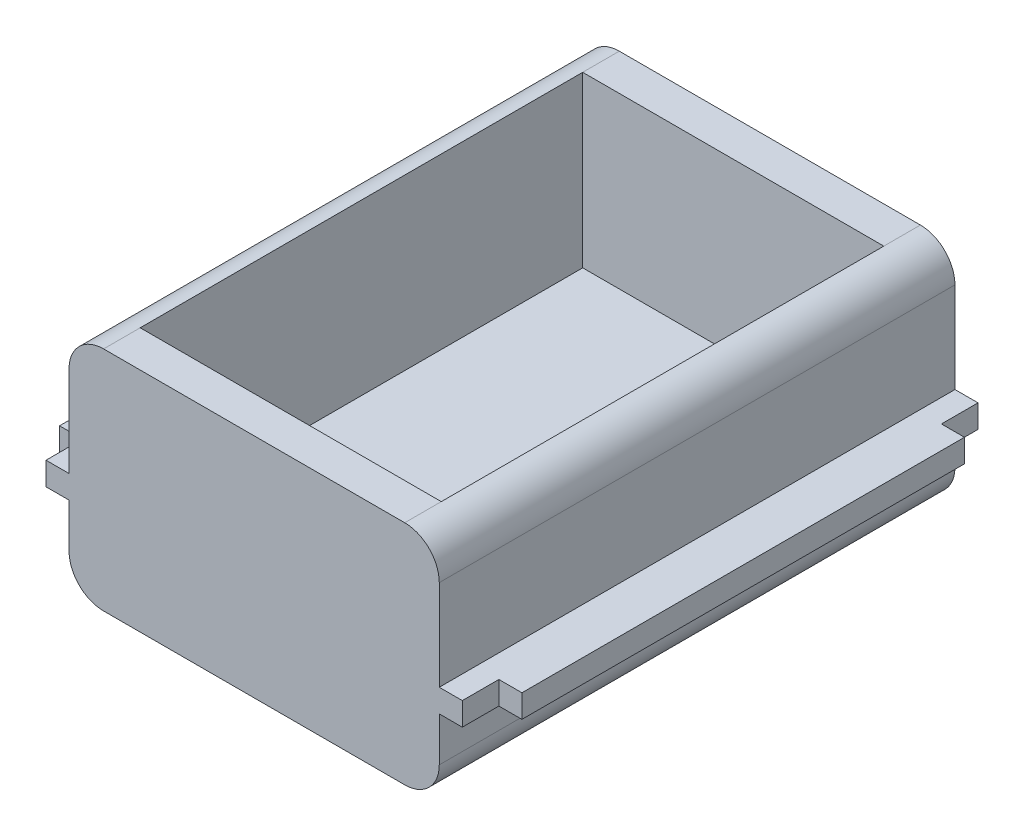
SolidWorks part; units mm, degrees
note: The reader was unsure of these and kept them because the rebuilt part matched: shared geometry of "Sketch5<4>".
ref_plane "Front Plane" through (0, 0, 0) normal (0, 0, 1) x (1, 0, 0)
ref_plane "Top Plane" through (0, 0, 0) normal (0, 1, 0) x (1, 0, 0)
ref_plane "Right Plane" through (0, 0, 0) normal (1, 0, 0) x (0, 0, -1)
ref_plane "Plane1" through (0, 0, 336.5649) normal (0, 0, 1) x (1, 0, 0)
sketch "Sketch3" plane through (0, 0, 336.5649) normal (0, 0, 1) x (1, 0, 0)
  line L1 (-13.0682, -2.8341) -> (13.0682, -2.8341)
  line L2 (-16.0682, 0.1659) -> (-16.0682, 13.8673)
  line L3 (-13.0682, 16.8673) -> (13.0682, 16.8673)
  line L8 (16.0682, 0.1659) -> (16.0682, 13.8673)
  line L9 (-16.0682, -10.0331) -> (16.0682, 29.6994) construction
  line L10 (-16.0682, 29.6994) -> (16.0682, -10.0331) construction
  arc A7 (13.0682, 16.8673) -> (16.0682, 13.8673) centre (13.0682, 13.8673) cw
  arc A8 (16.0682, 0.1659) -> (13.0682, -2.8341) centre (13.0682, 0.1659) cw
  arc A9 (-13.0682, -2.8341) -> (-16.0682, 0.1659) centre (-13.0682, 0.1659) cw
  arc A10 (-16.0682, 13.8673) -> (-13.0682, 16.8673) centre (-13.0682, 13.8673) cw
  point P0 (0, 9.8331)
  dimension "D1" = 3
  dimension "D2" = 32.1363
extrude "Boss-Extrude3" add sketch "Sketch3" against normal up to surface (43.175 mm away) and the other way up to surface (1.5875 mm away)
sketch "Sketch4" plane through (0, 16.8673, 0) normal (0, 1, 0) x (1, 0, 0)
  line L0 (13.0682, -293.3899) -> (13.0682, -338.1524) construction
  line L1 (-13.0682, -293.3899) -> (-13.0682, -338.1524) construction
  line L2 (13.0682, -296.5649) -> (13.0682, -334.9774)
  line L3 (-13.0682, -296.5649) -> (-13.0682, -334.9774)
  line L4 (-13.0682, -296.5649) -> (13.0682, -296.5649)
  line L6 (-31.6715, -334.9774) -> (26.9879, -334.9774) construction
  line L7 (-13.0682, -334.9774) -> (13.0682, -334.9774)
  line L9 (-35.6104, -296.5649) -> (31.9896, -296.5649) construction
extrude "Cut-Extrude1" cut sketch "Sketch4" against normal offset from surface (14.7014 mm away) 5 up to face at (0, -2.8341, 315.7712)
sketch "Sketch5" plane through (0, 0, 338.1524) normal (0, 0, 1) x (1, 0, 0)
  line L0 (-16.0682, 4) -> (-16.0682, 6)
  line L1 (-16.0682, 0.1659) -> (-16.0682, 13.8673) construction
  line L2 (-16.0682, 6) -> (-18.0682, 6)
  line L3 (-18.0682, 6) -> (-18.0682, 4)
  line L4 (-18.0682, 4) -> (-16.0682, 4)
  line L5 (0, 0) -> (0, 16.8673) construction
  line L6 (-13.0682, 16.8673) -> (13.0682, 16.8673) construction
  line L7 (16.0682, 4) -> (16.0682, 6)
  line L8 (18.0682, 4) -> (16.0682, 4)
  line L9 (18.0682, 6) -> (18.0682, 4)
  line L10 (16.0682, 6) -> (18.0682, 6)
  line L11 (20.0682, 6) -> (20.0682, 4)
  line L12 (-18.0682, 6) -> (-20.0682, 6)
  line L13 (-18.0682, 6) -> (-18.0682, 4)
  line L14 (-18.0682, 4) -> (-20.0682, 4)
  line L15 (-20.0682, 6) -> (-20.0682, 4)
  line L16 (18.0682, 6) -> (20.0682, 6)
  line L17 (18.0682, 4) -> (20.0682, 4)
  point P5 (-16.0682, 5)
  line M7 (-16.0682, 13.8673) -> (-16.0682, 0.1659)
  line M11 (16.0682, 0.1659) -> (16.0682, 13.8673)
  dimension "D1" = 2
  dimension "D2" = 2
  dimension "D3" = 2
  dimension "D4" = 2
  dimension "D5" = 5
extrude "Boss-Extrude5" add sketch "Sketch5" against normal up to surface (44.7625 mm away) contours L3 L4 L2 M7 | L10 L8 L9 M11
extrude "Boss-Extrude6" add sketch "Sketch5<4>" along normal up to surface (38.4125 mm away) from surface contours L9 L17 L11 L16 | L12 L15 L14 L13
sketch "Sketch5<4>" plane through (0, 0, 338.1524) normal (0, 0, 1) x (1, 0, 0) same geometry as "Sketch5"
